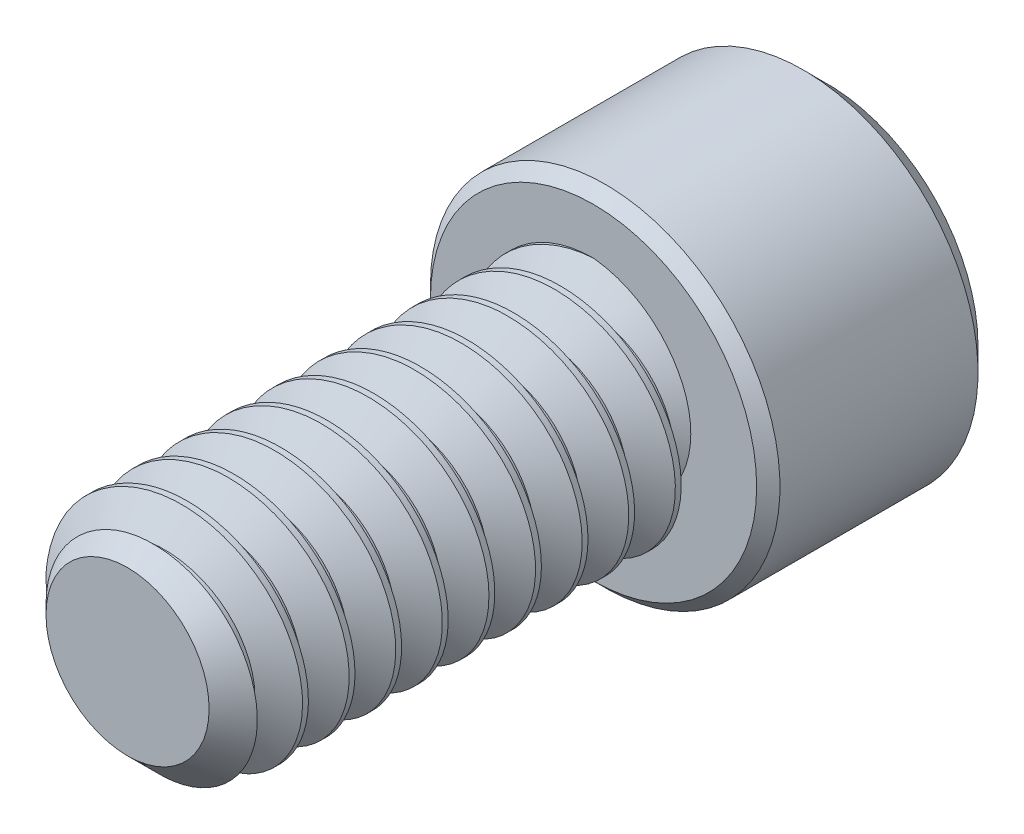
SolidWorks part; units mm, degrees
ref_plane "Front Plane" through (0, 0, 0) normal (0, 0, 1) x (1, 0, 0)
ref_plane "Top Plane" through (0, 0, 0) normal (0, 1, 0) x (1, 0, 0)
ref_plane "Right Plane" through (0, 0, 0) normal (1, 0, 0) x (0, 0, -1)
sketch "Sketch1" plane through (0, 0, 0) normal (0, 0, 1) x (1, 0, 0)
  line L0 (0, 3.175) -> (0, -3.175) construction
  circle A0 centre (0, 0) radius 3.175
  dimension "OD" = 6.35
extrude "Extrude1" add sketch "Sketch1" against normal blind 12.7
sketch "Sketch2" plane through (0, 0, 0) normal (0, 0, 1) x (1, 0, 0)
  circle A0 centre (0, 0) radius 3.175 construction
  circle A1 centre (0, 0) radius 3.175
curve "Helix/Spiral1" pitch 1.27 height 13.97 turns 11 parameters "pitch"=1.27
chamfer "Chamfer3" distance 0.9525 angle 45 1 edges at (3.175, 0, 0)
sketch "Sketch3" plane through (0, 0, 0) normal (1, 0, 0) x (0, 0, -1)
  line L0 (-1.1113, 3.175) -> (-0.635, 2.3501)
  line L1 (-0.635, 2.3501) -> (-0.4763, 2.3501)
  line L2 (-0.4763, 2.3501) -> (0, 3.175)
  line L3 (-1.1113, 3.175) -> (0, 3.175)
  line L4 (-0.5556, 3.175) -> (-0.5556, 2.3501) construction
  line L5 (-0.8731, 2.7626) -> (-0.2381, 2.7626) construction
  line L6 (0, 3.175) -> (0, -3.175) construction
  dimension "D1" = 0.1588
  dimension "D2" = 0.635
  dimension "D3" = 60
sweep "Cut-Sweep1" cut profiles "Sketch3" path "Helix/Spiral1"
sketch "Sketch6" plane through (0, 0, -12.7) normal (0, 0, -1) x (-1, 0, 0)
  circle A0 centre (0, 0) radius 4.7625
  dimension "head dia" = 9.525
extrude "Extrude2" add sketch "Sketch6" along normal blind 6.35
sketch "Sketch7" plane through (0, 0, -19.05) normal (0, 0, -1) x (-1, 0, 0)
  line L1 (0, 2.7496) -> (-2.3813, 1.3748)
  line L2 (-2.3813, 1.3748) -> (-2.3813, -1.3748)
  line L3 (-2.3813, -1.3748) -> (0, -2.7496)
  line L4 (0, -2.7496) -> (2.3813, -1.3748)
  line L5 (2.3813, -1.3748) -> (2.3813, 1.3748)
  line L6 (2.3813, 1.3748) -> (0, 2.7496)
  circle A0 centre (0, 0) radius 2.3813 construction
  dimension "hex dia" = 4.7625
extrude "Cut-Extrude1" cut sketch "Sketch7" against normal blind 3.5719
sketch "Sketch8" plane through (0, 0, -19.05) normal (0, 0, -1) x (-1, 0, 0)
  circle A0 centre (0, 0) radius 2.7496
extrude "Cut-Extrude2" cut sketch "Sketch8" against normal blind 0.635 draft 45
chamfer "Chamfer1" distance 0.635 angle 45 1 edges at (-4.7625, 0, -19.05)
chamfer "Chamfer2" distance 0.3175 angle 45 1 edges at (-4.7625, 0, -12.7)
sketch "Sketch9" plane through (0, 0, 0) normal (1, 0, 0) x (0, 0, -1)
  line L0 (0, 3.175) -> (0, -3.175) construction
  line L1 (6.985, 3.175) -> (6.985, -3.175) construction
  line L2 (12.7, 4.7625) -> (12.7, -4.7625) construction
  line L3 (19.05, 4.7625) -> (19.05, -4.7625) construction
  line L4 (19.05, 0) -> (0, 0) construction
  dimension "D1" = 6.985
  dimension "D2" = 6.35
  dimension "D3" = 9.525
  dimension "D4" = 12.7
equation "\"D3@Helix/Spiral1\" = \"screw length@Extrude1\"+\"pitch@Helix/Spiral1\""
equation "\"D1@Sketch3\" = \"pitch@Helix/Spiral1\"*.125"
equation "\"D2@Sketch3\" = \"pitch@Helix/Spiral1\"*.5"
equation "\"D1@Cut-Extrude1\" = \"hex dia@Sketch7\"*.75"
equation "\"D1@Chamfer1\" = \"head depth@Extrude2\"/10"
equation "\"D1@Sketch9\" = \"pitch@Helix/Spiral1\"*5.5"
equation "\"D1@Chamfer2\" = \"D1@Chamfer1\"/2"
equation "\"D1@Cut-Extrude2\" = \"D1@Chamfer2\"*2"
equation "\"D1@Chamfer3\" = \"pitch@Helix/Spiral1\"*.750"
equation "\"D2@Sketch9\" = \"head depth@Extrude2\""
equation "\"D3@Sketch9\" = \"head dia@Sketch6\""
equation "\"D4@Sketch9\" = \"screw length@Extrude1\""
